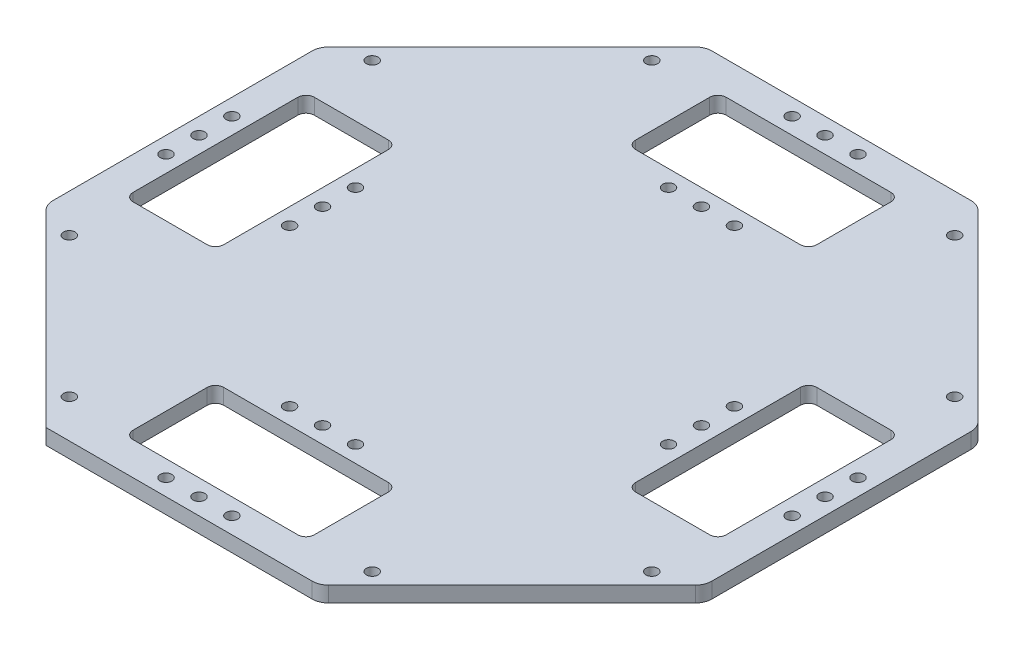
SolidWorks part; units mm, degrees
material "Custom Plastic"
ref_plane "Front Plane" through (0, 0, 0) normal (0, 0, 1) x (1, 0, 0)
ref_plane "Top Plane" through (0, 0, 0) normal (0, 1, 0) x (1, 0, 0)
ref_plane "Right Plane" through (0, 0, 0) normal (1, 0, 0) x (0, 0, -1)
ref_axis "Axis1" through (0, -0.2997, 0) along (0, 1, 0)
sketch "Base sketch" plane through (0, 0, 0) normal (0, 1, 0) x (1, 0, 0)
  line L1 (-127, 52.6051) -> (-127, -52.6051)
  line L2 (-127, -52.6051) -> (-52.6051, -127)
  line L3 (-52.6051, -127) -> (52.6051, -127)
  line L4 (52.6051, -127) -> (127, -52.6051)
  line L5 (127, -52.6051) -> (127, 52.6051)
  line L6 (127, 52.6051) -> (52.6051, 127)
  line L7 (52.6051, 127) -> (-52.6051, 127)
  line L8 (-52.6051, 127) -> (-127, 52.6051)
  circle A0 centre (0, 0) radius 127 construction
  dimension "D1" = 254
extrude "Base" add sketch "Base sketch" along normal blind 5.9944
sketch "Sketch3" plane through (0, 5.9944, 0) normal (0, 1, 0) x (1, 0, 0)
  line L0 (52.6051, 127) -> (-52.6051, 127) construction
  line L1 (-34.925, 114.3) -> (34.925, 114.3)
  line L2 (-34.925, 114.3) -> (-34.925, 79.375)
  line L4 (-34.925, 79.375) -> (34.925, 79.375)
  line L5 (34.925, 114.3) -> (34.925, 79.375)
  point P6 (0, 79.375)
  dimension "D1" = 69.85
  dimension "D2" = 34.925
  dimension "D3" = 12.7
extrude "Wheel cutout" cut sketch "Sketch3" against normal up to next
fillet "Wheel cutout fillets" radius 3.175 4 edges at (34.925, 2.9972, -114.3) (34.925, 2.9972, -79.375) (-34.925, 2.9972, -79.375) (-34.925, 2.9972, -114.3)
pattern_circular "Wheel cutout pattern" count 4 over 360 about axis through (0, -0.2997, 0) along (0, 1, 0) of "Wheel cutout", "Wheel cutout fillets"
fillet "Outside fillets" radius 6.35 7 edges at (-127, 2.9972, 52.6051) (-127, 2.9972, -52.6051) (-52.6051, 2.9972, -127) (52.6051, 2.9972, -127) (127, 2.9972, -52.6051) (127, 2.9972, 52.6051) (52.6051, 2.9972, 127)
hole_wizard "Bushing mounting holes (#8)" positions "Sketch7" profile "Sketch5" hole size "#8" standard "ANSI Inch" end condition up to next
sketch "Sketch7" plane through (0, 5.9944, 0) normal (0, 1, 0) x (1, 0, 0)
  line L0 (49.9749, 127) -> (-49.9749, 127) construction
  line L1 (-12.7, 120.65) -> (12.7, 120.65) construction
  line L2 (12.7, 73.025) -> (-12.7, 73.025) construction
  line L4 (31.75, 79.375) -> (-31.75, 79.375) construction
  point P0 (0, 120.65)
  point P2 (-12.7, 120.65)
  point P4 (12.7, 120.65)
  point P20 (12.7, 73.025)
  point P21 (-12.7, 73.025)
  point P31 (0, 73.025)
  dimension "D1" = 6.35
  dimension "D2" = 12.7
  dimension "D3" = 6.35
sketch "Sketch5" plane through (0, 5.9944, -120.65) normal (1, 0, 0) x (0, 0, 1)
  line L0 (0, 0) -> (0, 5.9954)
  line L1 (0, 5.9954) -> (2.2479, 5.9954)
  line L2 (2.2479, 5.9954) -> (2.2479, 0)
  line L5 (2.2479, 0) -> (0, 0)
  line L11 (0, -6.35) -> (0, 107.95) construction
  dimension "Thru Hole Dia." = 4.4958
  dimension "Thru Hole Depth" = 5.9954
pattern_circular "CirPattern2" count 4 over 360 about axis through (0, -0.2997, 0) along (0, 1, 0) of "Bushing mounting holes (#8)"
sketch "Sketch11" plane through (0, 5.9944, 0) normal (0, 1, 0) x (1, 0, 0)
  line L0 (0, 0) -> (-89.8026, 89.8026) construction
  line L1 (-54.465, 125.1401) -> (-125.1401, 54.465) construction
  line L2 (-112.2532, 58.3717) -> (-58.3717, 112.2532) construction
  point P7 (-85.3124, 85.3124)
  dimension "D1" = 76.2
  dimension "D2" = 6.35
hole_wizard "#8 Clearance Hole2" positions "Sketch13" profile "Sketch12" hole size "#8" standard "ANSI Inch"
sketch "Sketch13" plane through (0, 5.9944, 0) normal (0, 1, 0) x (1, 0, 0)
  point P0 (-112.2532, 58.3717)
  point P3 (-58.3717, 112.2532)
sketch "Sketch12" plane through (-112.2532, 5.9944, -58.3717) normal (1, 0, 0) x (0, 0, 1)
  line L0 (0, 0) -> (0, 5.9954)
  line L1 (0, 5.9954) -> (2.2479, 5.9954)
  line L2 (2.2479, 5.9954) -> (2.2479, 0)
  line L5 (2.2479, 0) -> (0, 0)
  line L10 (0, 5.9954) -> (-2.2479, 5.9954) construction
  line L11 (0, -6.35) -> (0, 107.95) construction
  dimension "Hole Dia." = 4.4958
  dimension "Hole Depth" = 5.9954
  dimension "Drill Angle" = 180
pattern_circular "CirPattern3" count 4 over 360 about axis through (0, -0.2997, 0) along (0, 1, 0) of "#8 Clearance Hole2"
